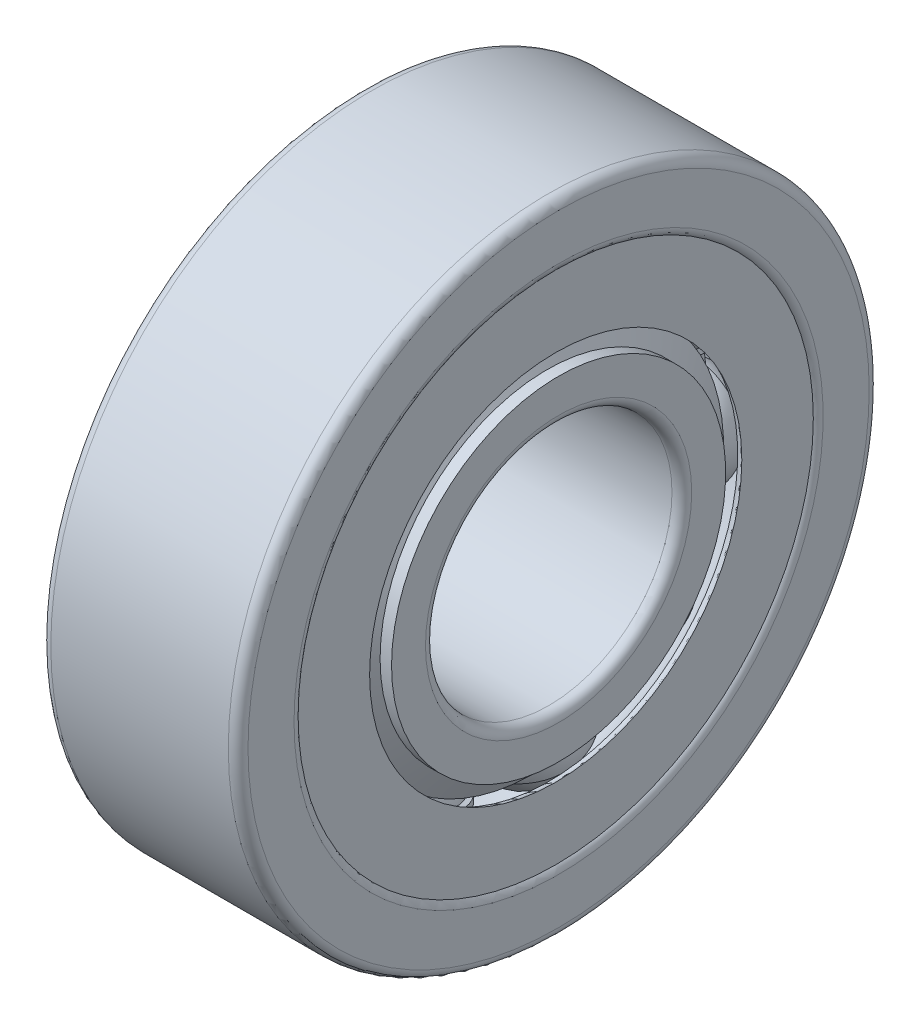
SolidWorks part; units mm, degrees
ref_plane "前视基准面" through (0, 0, 0) normal (0, 0, 1) x (1, 0, 0)
ref_plane "上视基准面" through (0, 0, 0) normal (0, 1, 0) x (1, 0, 0)
ref_plane "右视基准面" through (0, 0, 0) normal (1, 0, 0) x (0, 0, -1)
sketch "尺寸草图" plane through (0, 0, 0) normal (0, 0, 1) x (1, 0, 0)
  line L0 (-19.9271, 0) -> (19.9271, 0) construction
  line L1 (0, 21.603) -> (0, -21.603) construction
  line L2 (-1.8, 6.5) -> (1.8, 6.5)
  line L3 (2, 6.3) -> (2, 5.3667)
  line L4 (-2, 6.3) -> (-2, 5.3667)
  line L5 (-1.8, 5.1667) -> (1.8, 5.1667)
  line L6 (-3.5, 4.5) -> (3.3577, 4.5) construction
  line L7 (-1.8, 3.8333) -> (1.8, 3.8333)
  line L8 (2, 3.6333) -> (2, 2.7)
  line L9 (1.8, 2.5) -> (-1.8, 2.5)
  line L10 (-2, 2.7) -> (-2, 3.6333)
  line L11 (0, 4.5) -> (0, 5.5) construction
  line L13 (1.8, 5.1667) -> (1.8, 3.8333)
  line L14 (1.5111, 3.8333) -> (1.7677, 3.3889)
  line L15 (1.7677, 3.3889) -> (2, 3.3889)
  line L16 (1.9414, 5.2252) -> (1.9414, 3.7748)
  circle A0 centre (0, 4.5) radius 1
  arc A1 (2, 5.3667) -> (1.8, 5.1667) centre (1.8, 5.3667) cw
  arc A2 (2, 3.6333) -> (1.8, 3.8333) centre (1.8, 3.6333) ccw
  arc A3 (-1.8, 3.8333) -> (-2, 3.6333) centre (-1.8, 3.6333) ccw
  arc A4 (-1.8, 5.1667) -> (-2, 5.3667) centre (-1.8, 5.3667) cw
  arc A5 (-1.8, 2.5) -> (-2, 2.7) centre (-1.8, 2.7) cw
  arc A6 (1.8, 2.5) -> (2, 2.7) centre (1.8, 2.7) ccw
  arc A7 (2, 6.3) -> (1.8, 6.5) centre (1.8, 6.3) ccw
  arc A8 (-1.8, 6.5) -> (-2, 6.3) centre (-1.8, 6.3) ccw
  point P7 (0, 0)
  point P25 (-2, 3.8333)
  point P28 (-2, 5.1667)
  point P31 (-2, 2.5)
  point P36 (2, 6.5)
  point P39 (-2, 6.5)
  dimension "D1" = 0.3333
  dimension "D3" = 0.2
  dimension "B" = 4
  dimension "D2" = 2
  dimension "D" = 13
  dimension "(d)" = 5
  dimension "D5" = 4.5
  dimension "D6" = 1.3333
  dimension "D7" = 1.3333
  dimension "D8" = 0.4444
  dimension "D9" = 60
  dimension "D10" = 0.4889
sketch "草图2" plane through (0, 0, 0) normal (0, 0, 1) x (1, 0, 0)
  line L0 (1.5111, 3.8333) -> (1.7677, 3.3889) construction
  line L1 (1.7677, 3.3889) -> (2, 3.3889) construction
  line L2 (1.5111, 3.8333) -> (1.7677, 3.3889)
  line L3 (1.7677, 3.3889) -> (2, 3.3889)
  line L4 (0, 5.5) -> (0, 3.5) construction
  line L5 (-1.7677, 3.3889) -> (-2, 3.3889)
  line L6 (1.8, 2.5) -> (-1.8, 2.5) construction
  line L7 (-1.5111, 3.8333) -> (-1.7677, 3.3889)
  line L8 (-2, 6.3) -> (-2, 5.3667) construction
  line L9 (-1.8, 5.1667) -> (1.8, 5.1667) construction
  line L10 (-1.8, 6.5) -> (1.8, 6.5) construction
  line L11 (2, 6.3) -> (2, 5.3667) construction
  line L12 (2, 3.6333) -> (2, 2.7) construction
  line L13 (-1.8, 3.8333) -> (1.8, 3.8333) construction
  line L14 (1.8, 2.5) -> (-1.8, 2.5)
  line L15 (-2, 2.7) -> (-2, 3.6333) construction
  line L18 (-3.5, 0) -> (3.5, 0) construction
  line L19 (-19.9271, 0) -> (19.9271, 0) construction
  line L20 (-2, 6.3) -> (-2, 5.3667)
  line L21 (-1.8, 5.1667) -> (-0.7454, 5.1667)
  line L22 (-1.8, 6.5) -> (1.8, 6.5)
  line L23 (2, 6.3) -> (2, 5.3667)
  line L24 (2, 3.3889) -> (2, 2.7)
  line L25 (-1.5111, 3.8333) -> (-0.7454, 3.8333)
  line L26 (-2, 2.7) -> (-2, 3.3889)
  line L27 (0.7454, 5.1667) -> (1.8, 5.1667)
  line L28 (0.7454, 3.8333) -> (1.5111, 3.8333)
  circle A0 centre (0, 4.5) radius 1 construction
  arc A1 (0.7454, 5.1667) -> (-0.7454, 5.1667) centre (0, 4.5) ccw
  arc A2 (-0.7454, 3.8333) -> (0.7454, 3.8333) centre (0, 4.5) ccw
  arc A3 (-1.8, 6.5) -> (-2, 6.3) centre (-1.8, 6.3) ccw construction
  arc A4 (-2, 5.3667) -> (-1.8, 5.1667) centre (-1.8, 5.3667) ccw construction
  arc A5 (2, 6.3) -> (1.8, 6.5) centre (1.8, 6.3) ccw construction
  arc A6 (1.8, 5.1667) -> (2, 5.3667) centre (1.8, 5.3667) ccw construction
  arc A8 (1.8, 2.5) -> (2, 2.7) centre (1.8, 2.7) ccw construction
  arc A10 (-2, 2.7) -> (-1.8, 2.5) centre (-1.8, 2.7) ccw construction
  arc A11 (-1.8, 6.5) -> (-2, 6.3) centre (-1.8, 6.3) ccw
  arc A12 (-2, 5.3667) -> (-1.8, 5.1667) centre (-1.8, 5.3667) ccw
  arc A13 (2, 6.3) -> (1.8, 6.5) centre (1.8, 6.3) ccw
  arc A14 (1.8, 5.1667) -> (2, 5.3667) centre (1.8, 5.3667) ccw
  arc A16 (1.8, 2.5) -> (2, 2.7) centre (1.8, 2.7) ccw
  arc A18 (-2, 2.7) -> (-1.8, 2.5) centre (-1.8, 2.7) ccw
revolve "旋转1" add sketch "草图2" angle 360 about L18
sketch "草图5" plane through (0, 0, 0) normal (0, 0, 1) x (1, 0, 0)
  line L1 (-0.3, 4.3) -> (0.3, 4.3)
  line L2 (-0.3, 4.3) -> (-0.3, 4.7)
  line L3 (-0.3, 4.7) -> (0.3, 4.7)
  line L4 (0.3, 4.3) -> (0.3, 4.7)
  line L5 (-0.3, 4.3) -> (0.3, 4.7) construction
  line L6 (-0.3, 4.7) -> (0.3, 4.3) construction
  circle A0 centre (0, 4.5) radius 1 construction
  circle A1 centre (0, 4.5) radius 1 construction
  point P0 (0, 4.5)
  dimension "D3" = 2
  dimension "D1" = 0.6
  dimension "D2" = 0.4
revolve "旋转3" add sketch "草图5" angle 360 about L0
sketch "草图3" plane through (0, 0, 0) normal (0, 0, 1) x (1, 0, 0)
  line L1 (-1.1, 4.5) -> (1.1, 4.5)
  circle A0 centre (0, 4.5) radius 1 construction
  circle A1 centre (0, 4.5) radius 1 construction
  arc A2 (1.1, 4.5) -> (-1.1, 4.5) centre (0, 4.5) ccw
  dimension "D2" = 2.2
revolve "旋转2" add sketch "草图3" angle 360 about L1 region at (0, 4.9669, 0)
ref_axis "基准轴1" through (-3.85, 0, 0) along (1, 0, 0)
pattern_circular "阵列(圆周)5" count 11 over 360 about axis through (-3.85, 0, 0) along (1, 0, 0) of bodies 103
sketch "草图6" plane through (0, 0, 0) normal (0, 0, 1) x (1, 0, 0)
  line L0 (-1.0817, 4.7) -> (1.0817, 4.7)
  line L1 (-3.5, 4.5) -> (2, 4.5) construction
  line L3 (-1.0817, 4.3) -> (1.0817, 4.3)
  line L4 (2, -6.3) -> (2, 6.3) construction
  arc A0 (-1.0817, 4.3) -> (1.0817, 4.3) centre (0, 4.5) ccw
  circle A1 centre (0, 4.5) radius 1 construction
  circle A2 centre (0, 4.5) radius 1 construction
  arc A3 (1.0817, 4.7) -> (-1.0817, 4.7) centre (0, 4.5) ccw
  dimension "D1" = 2.2
  dimension "D2" = 2
  dimension "D3" = 0.2
  dimension "D4" = 0.2
revolve "切除-旋转1" cut sketch "草图6" angle 360 about L0
sketch "草图7" plane through (0, 0, 0) normal (0, 0, 1) x (1, 0, 0)
  line L0 (-1, 4.5) -> (1, 4.5)
  line L1 (-2, 0) -> (2.4587, 0) construction
  line L2 (-2, 6.3) -> (-2, -6.3) construction
  line L3 (-19.9271, 0) -> (19.9271, 0) construction
  circle A0 centre (0, 4.5) radius 1 construction
  arc A1 (1, 4.5) -> (-1, 4.5) centre (0, 4.5) ccw
revolve "旋转4" add sketch "草图7" angle 360 about L0
pattern_circular "阵列(圆周)2" count 11 over 360 about axis through (-3.85, 0, 0) along (1, 0, 0) of "旋转4" reverse direction yes
sketch "草图9" plane through (0, 0, 0) normal (0, 0, 1) x (1, 0, 0)
  line L1 (1.8, 5.1667) -> (1.8, 3.8333) construction
  line L4 (1.9414, 5.2252) -> (1.9414, 3.7748) construction
  line L5 (1.8, 5.1667) -> (1.8, 3.8333)
  line L6 (1.9414, 5.2252) -> (1.9414, 3.7748)
  line L7 (-1.9414, 5.2252) -> (-1.9414, 3.7748)
  line L8 (0, 6.5) -> (0, 0) construction
  line L9 (-1.8, 6.5) -> (1.8, 6.5) construction
  line L10 (-1.8, 5.1667) -> (-1.8, 3.8333)
  arc A0 (1.8, 5.1667) -> (2, 5.3667) centre (1.8, 5.3667) ccw construction
  arc A1 (1.8, 5.1667) -> (1.9414, 5.2252) centre (1.8, 5.3667) ccw
  arc A2 (2, 3.6333) -> (1.8, 3.8333) centre (1.8, 3.6333) ccw construction
  arc A3 (1.9414, 3.7748) -> (1.8, 3.8333) centre (1.8, 3.6333) ccw
  arc A4 (-1.9414, 3.7748) -> (-1.8, 3.8333) centre (-1.8, 3.6333) cw
  arc A5 (-1.8, 5.1667) -> (-1.9414, 5.2252) centre (-1.8, 5.3667) cw
revolve "旋转5" add sketch "草图9" angle 360 about L0
